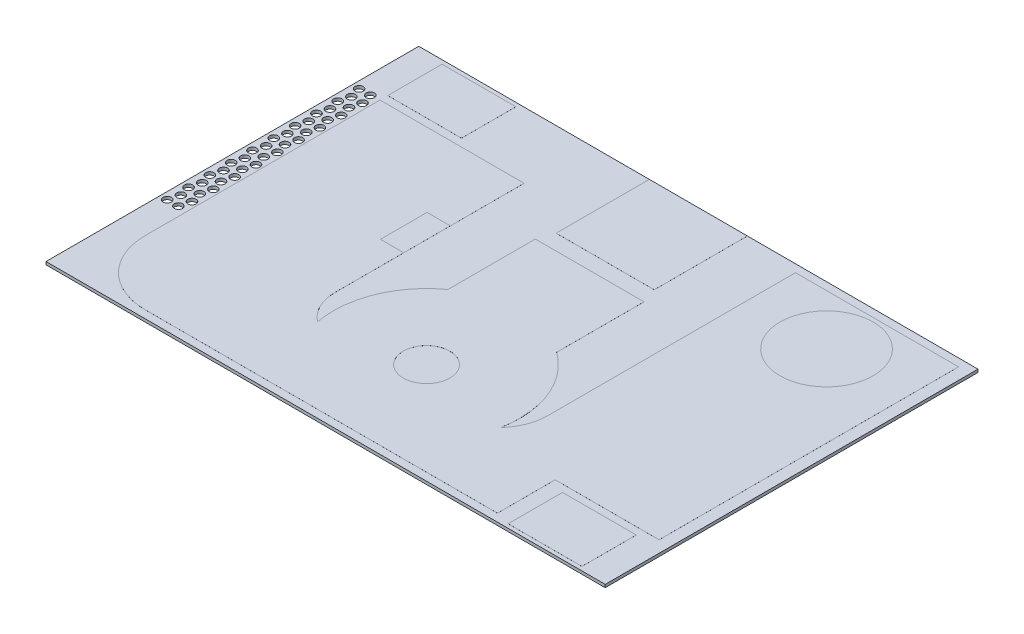
SolidWorks part; units mm, degrees
ref_plane "Front Plane" through (0, 0, 0) normal (0, 0, 1) x (1, 0, 0)
ref_plane "Top Plane" through (0, 0, 0) normal (0, 1, 0) x (1, 0, 0)
ref_plane "Right Plane" through (0, 0, 0) normal (1, 0, 0) x (0, 0, -1)
sketch "Sketch1" plane through (0, 0, 0) normal (0, 1, 0) x (1, 0, 0)
  line L1 (0, 0) -> (3657.6, 0)
  line L2 (0, 0) -> (0, 2438.4)
  line L3 (0, 2438.4) -> (3657.6, 2438.4)
  line L4 (3657.6, 0) -> (3657.6, 2438.4)
  dimension "D1" = 3657.6
  dimension "D2" = 2438.4
extrude "Grass" add sketch "Sketch1" against normal blind 19.05
sketch "Dimensions" plane through (0, 0, 0) normal (0, 1, 0) x (1, 0, 0)
  line L0 (1828.8, 2438.4) -> (1828.8, 0) construction
  line L1 (3657.6, 2438.4) -> (0, 2438.4) construction
  line L2 (0, 0) -> (3657.6, 0) construction
  line L3 (1219.2, 2438.4) -> (1219.2, 0) construction
  line L4 (2438.4, 2438.4) -> (2438.4, 0) construction
  line L5 (0, 2438.4) -> (0, 0) construction
  line L6 (3657.6, 0) -> (3657.6, 2438.4) construction
  line L7 (3048, 2387.6) -> (3048, 428.625) construction
  line L8 (177.8, 2006.6) -> (1120.775, 2006.6)
  line L9 (177.8, 2006.6) -> (177.8, 469.9)
  line L10 (596.9, 50.8) -> (1120.775, 50.8)
  line L11 (1120.775, 2006.6) -> (1120.775, 768.35)
  line L12 (177.8, 2413) -> (660.4, 2413)
  line L13 (177.8, 2413) -> (177.8, 2057.4)
  line L14 (177.8, 2057.4) -> (660.4, 2057.4)
  line L15 (660.4, 2413) -> (660.4, 2057.4)
  line L16 (2514.6, 2387.6) -> (3581.4, 2387.6)
  line L17 (2514.6, 2387.6) -> (2514.6, 768.35)
  line L18 (2514.6, 428.625) -> (3581.4, 428.625)
  line L19 (3581.4, 2387.6) -> (3581.4, 428.625)
  line L20 (1219.2, 546.1) -> (2438.4, 546.1) construction
  line L21 (3479.8, 25.4) -> (2997.2, 25.4)
  line L22 (3479.8, 25.4) -> (3479.8, 381)
  line L23 (3479.8, 381) -> (2997.2, 381)
  line L24 (2997.2, 25.4) -> (2997.2, 381)
  line L25 (1120.775, 50.8) -> (2901.95, 50.8)
  line L26 (1120.775, 50.8) -> (1120.775, 428.625)
  line L27 (1120.775, 428.625) -> (2901.95, 428.625)
  line L28 (2901.95, 50.8) -> (2901.95, 428.625)
  line L29 (1120.775, 768.35) -> (1120.775, 50.8)
  line L30 (2514.6, 768.35) -> (2514.6, 428.625)
  line L32 (1473.2, 1727.2) -> (2184.4, 1727.2)
  line L33 (1473.2, 1727.2) -> (1473.2, 1155.5372)
  line L34 (1473.2, 1155.5372) -> (2184.4, 1155.5372)
  line L35 (2184.4, 1727.2) -> (2184.4, 1155.5372)
  line L36 (1508.125, 2438.4) -> (2149.475, 2438.4)
  line L37 (1508.125, 2438.4) -> (1508.125, 1828.8)
  line L38 (1508.125, 1828.8) -> (2149.475, 1828.8)
  line L39 (2149.475, 2438.4) -> (2149.475, 1828.8)
  line L40 (1120.775, 1524) -> (968.375, 1524)
  line L41 (1120.775, 1524) -> (1120.775, 1219.2)
  line L42 (1120.775, 1219.2) -> (968.375, 1219.2)
  line L43 (968.375, 1524) -> (968.375, 1219.2)
  circle A0 centre (1828.8, 660.4) radius 152.4
  circle A1 centre (1828.8, 660.4) radius 609.6
  circle A2 centre (3048, 2057.4) radius 304.8
  arc A3 (177.8, 469.9) -> (596.9, 50.8) centre (596.9, 469.9) ccw
  arc A4 (1120.775, 768.35) -> (1230.0115, 546.1) centre (1401.4856, 768.35) ccw
  arc A5 (2514.6, 768.35) -> (2427.5885, 546.1) centre (2187.2521, 768.35) cw
  point P46 (1230.0115, 546.1)
  point P50 (2427.5885, 546.1)
  point P56 (1828.8, 1727.2)
  point P61 (1828.8, 1828.8)
  line M8 (3657.6, 2438.4) -> (0, 2438.4)
  dimension "D3" = 660.4
  dimension "D4" = 304.8
  dimension "D5" = 1219.2
  dimension "D17" = 609.6
  dimension "D19" = 25.4
  dimension "D24" = 419.1
  dimension "D1" = 1219.2
  dimension "D2" = 1219.2
  dimension "D6" = 177.8
  dimension "D7" = 431.8
  dimension "D8" = 942.975
  dimension "D9" = 50.8
  dimension "D10" = 482.6
  dimension "D11" = 355.6
  dimension "D12" = 25.4
  dimension "D13" = 50.8
  dimension "D14" = 428.625
  dimension "D15" = 76.2
  dimension "D16" = 1066.8
  dimension "D18" = 330.2
  dimension "D20" = 355.6
  dimension "D21" = 482.6
  dimension "D22" = 177.8
  dimension "D23" = 679.45
  dimension "D25" = 546.1
  dimension "D26" = 768.35
  dimension "D27" = 768.35
  dimension "D28" = 711.2
  dimension "D29" = 711.2
  dimension "D30" = 641.35
  dimension "D31" = 609.6
  dimension "D32" = 152.4
  dimension "D33" = 304.8
  dimension "D34" = 914.4
extrude "Street" add sketch "Dimensions" along normal blind 0.254 separate body contours L9 A3 L10 L26 L29 L11 L8 | A4 L29 L27 A1 | A1 L27 L26 L25 | L27 A1 L34 A0 | A1 L27 | L34 A1 | A1 L25 L28 L18 L27 | L17 L30 L18 L19 L16 A2 | L30 A5 A1 L27 | A1 L35 L32 L33 region at (646.9478, 0, -1038.5878) region at (1298.3633, 0, -195.0729) region at (1172.9844, 0, -522.9016) region at (2556.8602, 0, -219.5677) region at (1828.8, 0, -272.5873) region at (1275.7966, 0, -881.0693) region at (2471.7378, 0, -522.9125) region at (1828.8, 0, -1201.712) region at (1828.8, 0, -1479.1603) region at (3048, 0, -1302.7141)
extrude "Bases" add sketch "Sketch2<4>" along normal blind 0.254 separate body contours L15 L12 L13 L14 | L24 L21 L22 L23 region at (419.1, 0, -2235.2) region at (3238.5, 0, -203.2)
sketch "Sketch2<4>" plane through (0, 0, 0) normal (0, 1, 0) x (1, 0, 0) same geometry as "Dimensions"
extrude "Mt Simmons" add sketch "Dimensions<5>" along normal blind 0.254 separate body contours A2 region at (3048, 0, -2057.4)
sketch "Dimensions<5>" plane through (0, 0, 0) normal (0, 1, 0) x (1, 0, 0) same geometry as "Dimensions"
extrude "House" add sketch "Dimensions<6>" along normal blind 0.254 separate body contours L39 L37 L38 M8 region at (1828.8, 0, -2133.6)
sketch "Dimensions<6>" plane through (0, 0, 0) normal (0, 1, 0) x (1, 0, 0) same geometry as "Dimensions"
sketch "Sketch4" plane through (0, 0, 0) normal (0, 1, 0) x (1, 0, 0)
  line L0 (0, 2438.4) -> (0, 0) construction
  line L1 (3657.6, 2438.4) -> (0, 2438.4) construction
  circle A0 centre (46.0375, 2001.8375) radius 26.9875
  circle A1 centre (65.0875, 1932.1463) radius 26.9875
  circle A2 centre (46.0375, 1862.3915) radius 26.9875
  circle A3 centre (46.0375, 1722.9455) radius 26.9875
  circle A4 centre (46.0375, 1583.4995) radius 26.9875
  circle A5 centre (46.0375, 1444.0535) radius 26.9875
  circle A6 centre (46.0375, 1304.6075) radius 26.9875
  circle A7 centre (46.0375, 1165.1615) radius 26.9875
  circle A8 centre (46.0375, 1025.7155) radius 26.9875
  circle A9 centre (46.0375, 886.2695) radius 26.9875
  circle A10 centre (46.0375, 746.8235) radius 26.9875
  circle A11 centre (65.0875, 1792.7638) radius 26.9875
  circle A12 centre (65.0875, 1653.3813) radius 26.9875
  circle A13 centre (65.0875, 1513.9988) radius 26.9875
  circle A14 centre (65.0875, 1374.6163) radius 26.9875
  circle A15 centre (65.0875, 1235.2338) radius 26.9875
  circle A16 centre (65.0875, 1095.8513) radius 26.9875
  circle A17 centre (65.0875, 956.4688) radius 26.9875
  circle A18 centre (65.0875, 817.0863) radius 26.9875
  circle A19 centre (138.1125, 1792.7638) radius 26.9875
  circle A20 centre (138.1125, 1653.3813) radius 26.9875
  circle A21 centre (138.1125, 1513.9988) radius 26.9875
  circle A22 centre (138.1125, 1374.6163) radius 26.9875
  circle A23 centre (138.1125, 1235.2338) radius 26.9875
  circle A24 centre (138.1125, 1095.8513) radius 26.9875
  circle A25 centre (138.1125, 956.4688) radius 26.9875
  circle A26 centre (138.1125, 817.0863) radius 26.9875
  circle A27 centre (138.1125, 1932.1463) radius 26.9875
  circle A28 centre (119.1895, 2001.8375) radius 26.9875
  circle A29 centre (119.1895, 1862.3915) radius 26.9875
  circle A30 centre (119.1895, 1722.9455) radius 26.9875
  circle A31 centre (119.1895, 1583.4995) radius 26.9875
  circle A32 centre (119.1895, 1444.0535) radius 26.9875
  circle A33 centre (119.1895, 1304.6075) radius 26.9875
  circle A34 centre (119.1895, 1165.1615) radius 26.9875
  circle A35 centre (119.1895, 1025.7155) radius 26.9875
  circle A36 centre (119.1895, 886.2695) radius 26.9875
  circle A37 centre (119.1895, 746.8235) radius 26.9875
  dimension "D1" = 53.975
  dimension "D3" = 65.0875
  dimension "D2" = 436.5625
  dimension "D4" = 69.6912
  dimension "D9" = 46.0375
  dimension "D5" = 10
  dimension "D6" = 9
  dimension "D7" = 2
  dimension "D8" = 2
extrude "Cut-Extrude3" cut sketch "Sketch4" against normal up to next (19.05 mm away) draft 1
extrude "Parking" add sketch "Dimensions<8>" along normal blind 0.254 separate body contours L40 L43 L42 L11 region at (1044.575, 0, -1371.6)
sketch "Dimensions<8>" plane through (0, 0, 0) normal (0, 1, 0) x (1, 0, 0) same geometry as "Dimensions"
